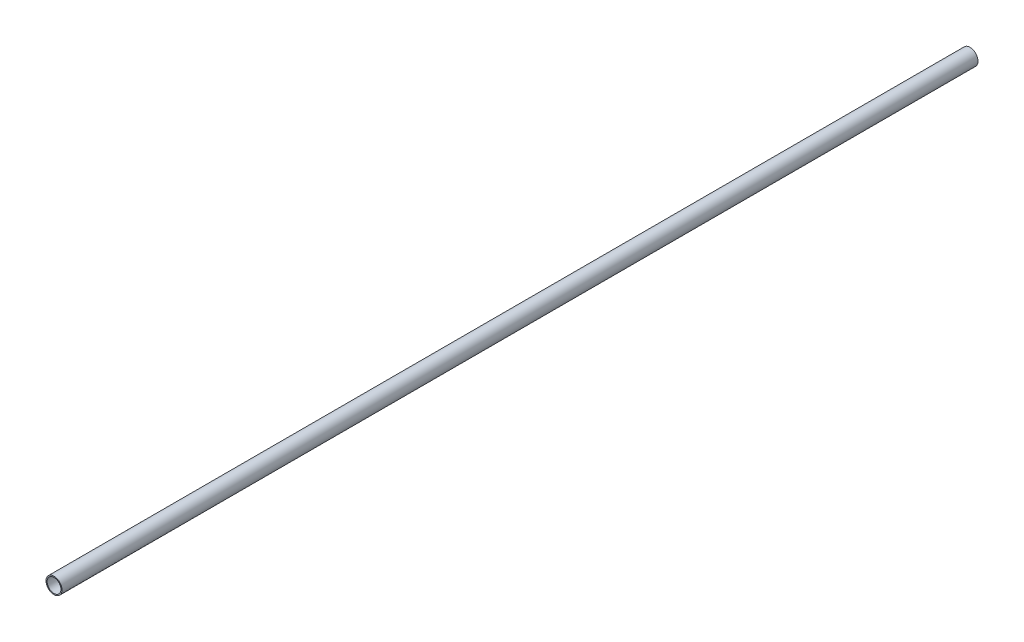
SolidWorks part; units mm, degrees
material "PET"
ref_plane "Front Plane" through (0, 0, 0) normal (0, 0, 1) x (1, 0, 0)
ref_plane "Top Plane" through (0, 0, 0) normal (0, 1, 0) x (1, 0, 0)
ref_plane "Right Plane" through (0, 0, 0) normal (1, 0, 0) x (0, 0, -1)
ref_axis "Centre Axis" through (0, 0, -34.5703) along (0, 0, 1)
sketch "Sketch1" plane through (0, 0, 0) normal (0, 0, 1) x (1, 0, 0)
  circle A0 centre (0, 0) radius 3.675
  circle A1 centre (0, 0) radius 3.175
  dimension "D1" = 0.5
  dimension "D2" = 6.35
extrude "Boss-Extrude1" add sketch "Sketch1" along normal blind 420
